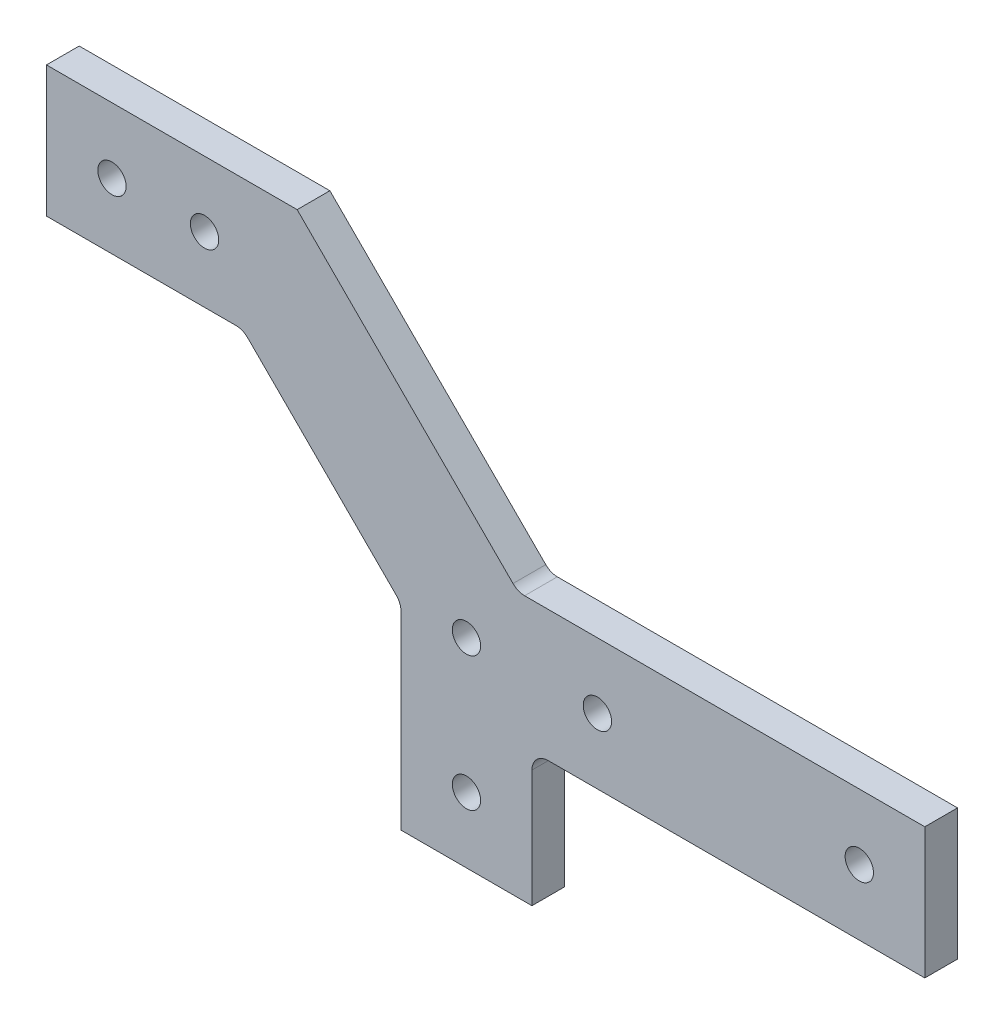
SolidWorks part; units mm, degrees
material "6061-T6 (SS)"
ref_plane "Front" through (0, 0, 0) normal (0, 0, 1) x (1, 0, 0)
ref_plane "Top" through (0, 0, 0) normal (0, 1, 0) x (1, 0, 0)
ref_plane "Right" through (0, 0, 0) normal (1, 0, 0) x (0, 0, -1)
sketch "Sketch4" plane through (-292.1, 0, 0) normal (0, 0, 1) x (1, 0, 0)
  line L0 (292.1, 63.5) -> (292.1, 0)
  line L1 (342.1, 0) -> (242.1, 0) construction
  line L2 (292.1, 63.5) -> (254, 101.6)
  line L4 (254, 101.6) -> (-254, 101.6)
  line L5 (292.1, 0) -> (-292.1, 0) construction
  line L6 (-254, 101.6) -> (-292.1, 63.5)
  line L7 (-292.1, 63.5) -> (-292.1, -25.4)
  dimension "D1" = 90
sketch "Sketch1" plane through (0, 0, 0) normal (0, 0, 1) x (1, 0, 0)
  line L0 (-12.7, 46.1) -> (-12.7, 58.2395)
  line L1 (12.7, 71.5) -> (88.9, 71.5)
  line L2 (88.9, 71.5) -> (88.9, 46.1)
  line L3 (88.9, 46.1) -> (12.7, 46.1)
  line L6 (-12.7, 58.2395) -> (-43.3605, 88.9)
  line L7 (-43.3605, 88.9) -> (-81.4605, 88.9)
  line L8 (-81.4605, 88.9) -> (-81.4605, 114.3)
  line L9 (-81.4605, 114.3) -> (-32.8395, 114.3)
  line L10 (-32.8395, 114.3) -> (9.9605, 71.5)
  line L11 (9.9605, 71.5) -> (12.7, 71.5)
  line L12 (-12.7, 46.1) -> (-12.7, 0) construction
  line L13 (0, 63.5) -> (-38.1, 101.6) construction
  line L14 (-38.1, 101.6) -> (-546.1, 101.6) construction
  line L15 (12.7, 71.5) -> (-12.7, 71.5) construction
  line L16 (-12.7, 71.5) -> (-12.7, 58.2395) construction
  line L17 (12.7, 46.1) -> (12.7, 20.1395)
  line L18 (12.7, 20.1395) -> (-12.7, 20.1395)
  line L19 (-12.7, 20.1395) -> (-12.7, 46.1)
  line L20 (12.7, 46.1) -> (-12.7, 46.1) construction
  line L21 (12.7, 71.5) -> (12.7, 46.1) construction
  line L22 (0, 0) -> (-584.2, 0) construction
  line L23 (0, 20.1395) -> (0, 0) construction
  dimension "D1" = 46.1
  dimension "D2" = 25.4
  dimension "D3" = 38.1
  dimension "D4" = 101.6
  dimension "D5" = 12.7
  dimension "D6" = 12.7
  dimension "D7" = 12.7
  dimension "D8" = 12.7
  dimension "D9" = 38.1
  dimension "D10" = 25.4
extrude "Boss-Extrude1" add sketch "Sketch1" along normal blind 6.35
fillet "Fillet1" radius 3.175 4 edges at (-43.3605, 88.9, 3.175) (-12.7, 58.2395, 3.175) (12.7, 46.1, 3.175) (9.9605, 71.5, 3.175)
hole_wizard "M5 Clearance Hole1" positions "Sketch2" profile "Sketch3" hole size "M5" standard "ANSI Metric"
sketch "Sketch2" plane through (0, 0, 6.35) normal (0, 0, 1) x (1, 0, 0)
  line L5 (88.9, 71.5) -> (76.2, 58.8) construction
  line L6 (76.2, 58.8) -> (88.9, 46.1) construction
  line L8 (76.2, 58.8) -> (25.4, 58.8) construction
  line L12 (25.4, 58.8) -> (0, 58.8) construction
  line L14 (-81.4605, 114.3) -> (-68.7605, 101.6) construction
  line L15 (-68.7605, 101.6) -> (-81.4605, 88.9) construction
  line L17 (-68.7605, 101.6) -> (-50.8, 101.6) construction
  line L22 (12.7, 20.1395) -> (0, 32.8395) construction
  line L23 (0, 32.8395) -> (-12.7, 20.1395) construction
  line L25 (0, 32.8395) -> (0, 58.8) construction
  point P0 (0, 58.8)
  point P4 (25.4, 58.8)
  point P6 (76.2, 58.8)
  point P48 (-50.8, 101.6)
  point P50 (-68.7605, 101.6)
  point P87 (0, 32.8395)
  point P91 (0, 0)
  point P92 (0, 0)
  dimension "D1" = 50.8
  dimension "D4" = 12.7
sketch "Sketch3" plane through (0, 58.8, 6.35) normal (1, 0, 0) x (0, -1, 0)
  line L0 (0, 0) -> (0, 20.4024)
  line L1 (0, 20.4024) -> (2.75, 18.75)
  line L2 (2.75, 18.75) -> (2.75, 0)
  line L5 (2.75, 0) -> (0, 0)
  line L10 (0, 20.4024) -> (-2.75, 18.75) construction
  line L11 (0, -6.35) -> (0, 107.95) construction
  dimension "Hole Dia." = 5.5
  dimension "Hole Depth" = 18.75
  dimension "Drill Angle" = 118
